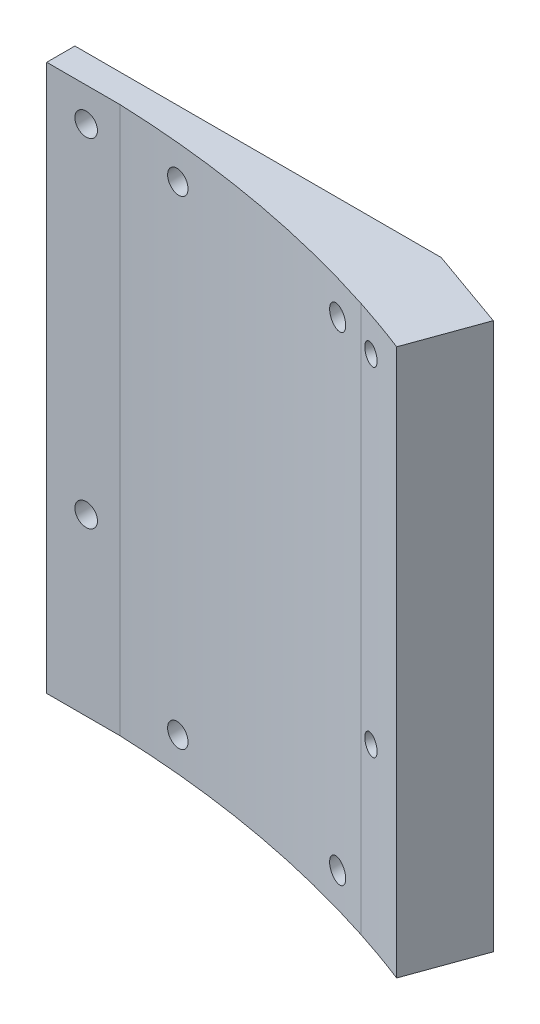
SolidWorks part; units mm, degrees
ref_plane "Front Plane" through (0, 0, 0) normal (0, 0, 1) x (1, 0, 0)
ref_plane "Top Plane" through (0, 0, 0) normal (0, 1, 0) x (1, 0, 0)
ref_plane "Right Plane" through (0, 0, 0) normal (1, 0, 0) x (0, 0, -1)
sketch "Sketch2" plane through (0, 0, 0) normal (0, 1, 0) x (1, 0, 0)
  line L0 (-120, 144.0703) -> (120, 144.0703) construction
  line L2 (6, 187.5) -> (58, 187.5) construction
  line L3 (58, 187.5) -> (58, 302.5) construction
  line L8 (58, 302.5) -> (0, 302.5) construction
  line L9 (0, 302.5) -> (0, 228.1791) construction
  line L10 (0, 228.1791) -> (58, 228.1791) construction
  line L11 (0, 144.0703) -> (0, 334.8408) construction
  line L32 (7.4972, 192.5) -> (58, 192.5)
  line L34 (7.4972, 192.5) -> (-7, 192.5)
  line L35 (-7, 192.5) -> (-7, 187.5)
  line L36 (-7, 187.5) -> (6, 187.5)
  line L37 (62.7337, 176.6939) -> (67.1159, 189.0366) construction
  line L38 (58, 192.5) -> (72.1308, 187.483)
  line L39 (62.7337, 176.6939) -> (53.0987, 180.0309) construction
  line L40 (72.3298, 187.411) -> (67.7777, 174.8211)
  line L41 (72.1308, 187.483) -> (72.3298, 187.411)
  arc A0 (120, 144.0703) -> (-116.9975, 146.5191) centre (0, 0) ccw construction
  spline S1 degree 2 poles (6, 187.5) (32.6742, 186.4915) (58, 178.3038) knots 0 0 0 1 1 1
  spline S2 degree 2 poles (58, 178.3038) (62.9372, 176.6978) (67.7777, 174.8211) knots 0 0 0 1 1 1
  dimension "D1" = 375
  dimension "D2" = 240
  dimension "D3" = 52
  dimension "D4" = 115
  dimension "D5" = 58
  dimension "D17" = 90
  dimension "D18" = 5
  dimension "D19" = 7
  dimension "D20" = 5
  dimension "D21" = 5.25
extrude "Boss-Extrude1" add sketch "Sketch2" along normal blind 120
sketch "Sketch7" plane through (0, 0, -192.5) normal (0, 0, -1) x (-1, 0, 0)
  line L0 (-58, 120) -> (-58, 0) construction
  line L1 (-7.4972, 0) -> (-58, 0) construction
  line L2 (-58, 48.5) -> (-23.134, 48.5) construction
  line L3 (-58, 97) -> (7, 97)
  line L4 (7, 120) -> (7, 0) construction
  line L5 (7, 97) -> (7, 120)
  line L6 (7, 120) -> (-58, 120)
  line L7 (-58, 120) -> (-58, 97)
  circle A0 centre (-17, 6) radius 2
  circle A1 centre (-52, 6) radius 2
  circle A2 centre (-17, 91) radius 2
  circle A3 centre (-52, 91) radius 2
  circle A4 centre (0, 31) radius 2
  circle A5 centre (0, 91) radius 2
  dimension "D1" = 4
  dimension "D2" = 4
  dimension "D9" = 4
  dimension "D10" = 4
  dimension "D3" = 35
  dimension "D4" = 6
  dimension "D5" = 6
  dimension "D6" = 6
  dimension "D7" = 42.5
  dimension "D8" = 6
  dimension "D11" = 60
  dimension "D12" = 7
  dimension "D13" = 6
  dimension "D14" = 7
extrude "Cut-Extrude3" cut sketch "Sketch7" against normal blind 20
sketch "Sketch8" plane through (67.1874, 0, -189.2381) normal (0.3346, 0, -0.9424) x (-0.9424, 0, -0.3346)
  line L1 (2.2493, 91) -> (2.2493, 31) construction
  line L2 (9.7493, 97) -> (9.7493, 0) construction
  line L3 (9.7493, 97) -> (-5.2456, 97)
  line L4 (-5.2456, 120) -> (-5.2456, 0) construction
  line L6 (-5.2456, 120) -> (9.7493, 120)
  line L7 (9.7493, 120) -> (9.7493, 97)
  line L8 (-5.2456, 120) -> (-14.1393, 120)
  line L9 (-14.1393, 120) -> (-14.1393, 97)
  line L10 (-14.1393, 97) -> (-5.2456, 97)
  circle A0 centre (2.2493, 31) radius 1.75
  circle A1 centre (2.2493, 91) radius 1.75
  dimension "D1" = 3.5
  dimension "D3" = 3.5
  dimension "D2" = 6
  dimension "D4" = 60
  dimension "D5" = 7.5
extrude "Cut-Extrude4" cut sketch "Sketch8" against normal blind 20
